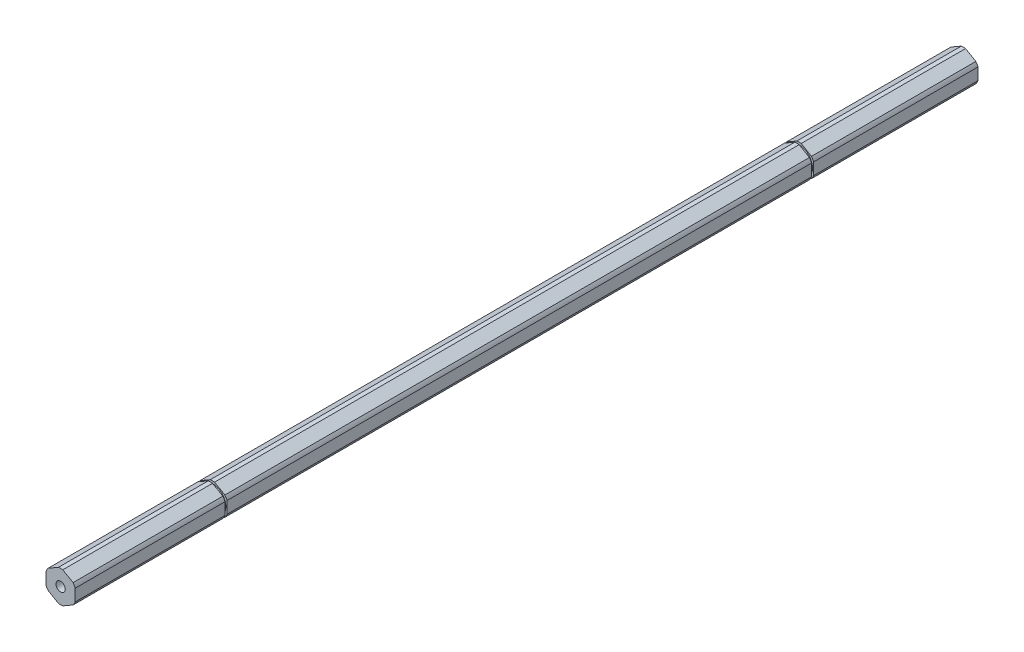
SolidWorks part; units mm, degrees
material "6061-T6 (SS)"
ref_plane "Front Plane" through (0, 0, 0) normal (0, 0, 1) x (1, 0, 0)
ref_plane "Top Plane" through (0, 0, 0) normal (0, 1, 0) x (1, 0, 0)
ref_plane "Right Plane" through (0, 0, 0) normal (1, 0, 0) x (0, 0, -1)
sketch "Sketch1" plane through (0, 0, 0) normal (0, 0, 1) x (1, 0, 0)
  line L1 (0, 7.3323) -> (-6.35, 3.6662)
  line L2 (-6.35, 3.6662) -> (-6.35, -3.6662)
  line L3 (-6.35, -3.6662) -> (0, -7.3323)
  line L4 (0, -7.3323) -> (6.35, -3.6662)
  line L5 (6.35, -3.6662) -> (6.35, 3.6662)
  line L6 (6.35, 3.6662) -> (0, 7.3323)
  circle A0 centre (0, 0) radius 6.35 construction
  circle A1 centre (0, 0) radius 6.858
  dimension "D1" = 12.7
  dimension "D2" = 13.716
extrude "Boss-Extrude1" add sketch "Sketch1" along normal mid plane 392.303 contours L5 A1 L6 L1 L2 L3 L4 region at (0, 0, 0)
sketch "Sketch2" plane through (0, 0, 196.1515) normal (0, 0, 1) x (1, 0, 0)
  circle A0 centre (0, 0) radius 2.0193
  dimension "D1" = 4.0386
extrude "Cut-Extrude1" cut sketch "Sketch2" against normal through all
sketch "Sketch4" plane through (0, 0, 0) normal (0, 1, 0) x (1, 0, 0)
  line L0 (-2.0193, -196.1515) -> (2.0193, -196.1515) construction
  line L5 (-0.9317, -196.1515) -> (0.9317, -196.1515) construction
  line L7 (9.0297, 124.7267) -> (5.8547, 124.7267)
  line L8 (9.0297, 124.7267) -> (9.0297, 123.8377)
  line L9 (9.0297, 123.8377) -> (5.8547, 123.8377)
  line L10 (5.8547, 124.7267) -> (5.8547, 123.8377)
  line L11 (5.8547, -131.0767) -> (9.0297, -131.0767)
  line L12 (0, 196.1515) -> (0, -196.1515) construction
  line L13 (2.0193, 196.1515) -> (-2.0193, 196.1515) construction
  line L14 (5.8547, -131.0767) -> (5.8547, -130.1877)
  line L15 (5.8547, -130.1877) -> (9.0297, -130.1877)
  line L16 (9.0297, -131.0767) -> (9.0297, -130.1877)
  dimension "D1" = 0.889
  dimension "D2" = 392.303
  dimension "D3" = 5.8547
  dimension "D4" = 71.4248
  dimension "D5" = 3.175
  dimension "D6" = 3.175
  dimension "D7" = 0.889
  dimension "D8" = 65.0748
revolve "Cut-Revolve4" cut sketch "Sketch4" angle 360 about L12
